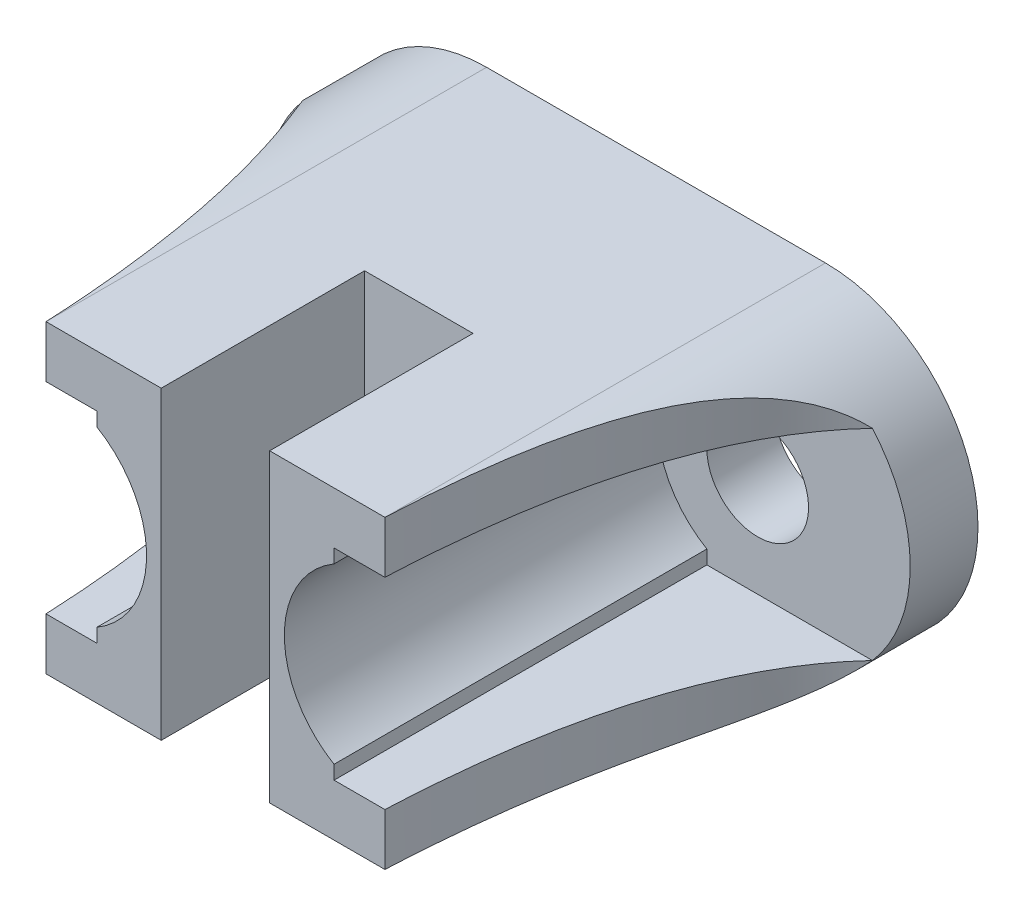
SolidWorks part; units mm, degrees
ref_plane "Front Plane" through (0, 0, 0) normal (0, 0, 1) x (1, 0, 0)
ref_plane "Top Plane" through (0, 0, 0) normal (0, 1, 0) x (1, 0, 0)
ref_plane "Right Plane" through (0, 0, 0) normal (1, 0, 0) x (0, 0, -1)
sketch "Sketch1" plane through (0, 0, 0) normal (0, 0, 1) x (1, 0, 0)
  line L0 (0, 0) -> (-53.4604, 0) construction
  line L1 (0, 33.9369) -> (0, 0) construction
  line L2 (-5, 4.5) -> (5, 4.5)
  line L3 (-5, 0) -> (-5, -5.0813) construction
  line L4 (-5, -4.5) -> (5, -4.5)
  circle A0 centre (-5, 0) radius 1.5
  arc A1 (-5, 4.5) -> (-5, -4.5) centre (-5, 0) ccw
  circle A2 centre (5, 0) radius 1.5
  arc A3 (5, 4.5) -> (5, -4.5) centre (5, 0) cw
  point P12 (0, -4.5)
  point P15 (0, 4.5)
  dimension "D1" = 3
  dimension "D2" = 3
  dimension "D3" = 5
extrude "Boss-Extrude1" add sketch "Sketch1" along normal blind 2
sketch "Sketch2" plane through (0, 0, 2) normal (0, 0, 1) x (1, 0, 0)
  line L0 (0, 0) -> (0, 5.9502) construction
  line L1 (5, 4.5) -> (-5, 4.5) construction
  line L3 (-1.6, 4.5) -> (-1.6, -4.5)
  line L5 (1.6, 4.5) -> (1.6, -4.5)
  line L6 (-5, -4.5) -> (5, -4.5) construction
  line L8 (-1.6, 4.5) -> (-3.5, 4.5)
  line L9 (-1.6, 4.5) -> (-1.6, -4.5)
  line L10 (-1.6, -4.5) -> (-3.5, -4.5)
  line L11 (-3.5, 4.5) -> (-3.5, -4.5)
  line L12 (1.6, 4.5) -> (3.5, 4.5)
  line L13 (1.6, 4.5) -> (1.6, -4.5)
  line L14 (1.6, -4.5) -> (3.5, -4.5)
  line L15 (3.5, 4.5) -> (3.5, -4.5)
  line M3 (-5, -4.5) -> (5, -4.5)
  line M5 (5, 4.5) -> (-5, 4.5)
  dimension "D1" = 1.6
  dimension "D2" = 1.6
extrude "Boss-Extrude2" add sketch "Sketch2" along normal blind 5 contours L11 L3 M5 M3 | L5 L3 M5 M3 | L15 L5 M5 M3 region at (0, 0, 2) region at (-2.55, 0, 2) region at (2.55, 0, 2)
extrude "Boss-Extrude3" add sketch "Sketch2<3>" along normal blind 11 contours L11 L3 M5 M3 | L15 L5 M5 M3 region at (-2.55, 0, 2) region at (2.55, 0, 2)
sketch "Sketch2<3>" plane through (0, 0, 2) normal (0, 0, 1) x (1, 0, 0) same geometry as "Sketch2"
sketch "Sketch3" plane through (0, 0, 2) normal (0, 0, 1) x (1, 0, 0)
  line L0 (-10.0193, 0) -> (9.5, 0) construction
  line L1 (-3.5, 4.5) -> (-5, 4.5)
  line L2 (-3.5, 4.5) -> (-3.5, 2.9669)
  line L3 (-3.5, 2.9669) -> (-8.3834, 2.9669)
  line L4 (0, 5.6928) -> (0, -7.8511) construction
  line L5 (-3.5, -2.9669) -> (-8.3834, -2.9669)
  line L6 (-3.5, -4.5) -> (-3.5, -2.9669)
  line L7 (-3.5, -4.5) -> (-5, -4.5)
  line L8 (3.5, -4.5) -> (5, -4.5)
  line L9 (3.5, -4.5) -> (3.5, -2.9669)
  line L10 (3.5, -2.9669) -> (8.3834, -2.9669)
  line L11 (3.5, 2.9669) -> (8.3834, 2.9669)
  line L12 (3.5, 4.5) -> (3.5, 2.9669)
  line L13 (3.5, 4.5) -> (5, 4.5)
  arc A0 (-5, 4.5) -> (-5, -4.5) centre (-5, 0) ccw construction
  arc A1 (-5, 4.5) -> (-8.3834, 2.9669) centre (-5, 0) ccw
  arc A2 (5, 4.5) -> (8.3834, 2.9669) centre (5, 0) cw
  arc A3 (-8.3834, -2.9669) -> (-5, -4.5) centre (-5, 0) ccw
  arc A4 (8.3834, -2.9669) -> (5, -4.5) centre (5, 0) cw
extrude "Boss-Extrude4" add sketch "Sketch3" along normal blind 11
sketch "Sketch4" plane through (0, 0, 0) normal (0, 1, 0) x (1, 0, 0)
  line L0 (0, 0) -> (0, -13.9749) construction
  line L1 (-8.3834, -2) -> (-12.2964, -13.1828)
  line L2 (-12.2964, -13.1828) -> (-6.0789, -14.3511)
  line L3 (-6.0789, -14.3511) -> (-5, -13)
  line L4 (5, -13) -> (8.3834, -14.7075)
  line L5 (8.3834, -14.7075) -> (10.5143, -13.9749)
  line L6 (10.5143, -13.9749) -> (8.3834, -2)
  spline S0 degree 2 poles (-8.3834, -2) (-5.3543, -5.2365) (-5, -13) knots 0 0 0 1 1 1
  spline S1 degree 2 poles (8.3834, -2) (5.3543, -5.2365) (5, -13) knots 0 0 0 1 1 1
extrude "Cut-Extrude1" cut sketch "Sketch4" against normal through all and the other way through all
sketch "Sketch5" plane through (0, 0, 13) normal (0, 0, 1) x (1, 0, 0)
  circle A0 centre (-5, 0) radius 2.9669
  circle A1 centre (5, 0) radius 2.9669
extrude "Cut-Extrude2" cut sketch "Sketch5" against normal up to surface (11 mm away) up to face at (-5.3139, 0.4945, 2)
